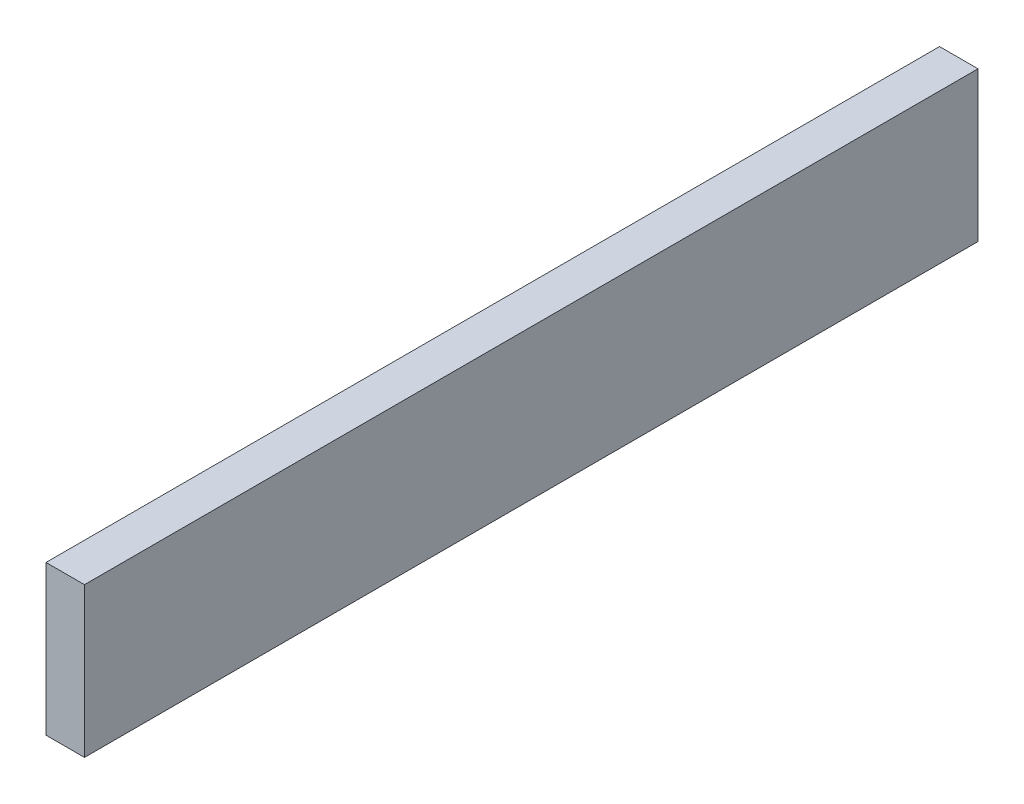
SolidWorks part; units mm, degrees
ref_plane "Front Plane" through (0, 0, 0) normal (0, 0, 1) x (1, 0, 0)
ref_plane "Top Plane" through (0, 0, 0) normal (0, 1, 0) x (1, 0, 0)
ref_plane "Right Plane" through (0, 0, 0) normal (1, 0, 0) x (0, 0, -1)
sketch "Sketch1" plane through (0, 0, 0) normal (1, 0, 0) x (0, 0, -1)
  line L1 (0, 0) -> (418, 0)
  line L2 (0, 0) -> (0, 70)
  line L3 (0, 70) -> (418, 70)
  line L4 (418, 0) -> (418, 70)
  dimension "D1" = 418
  dimension "D2" = 70
extrude "Boss-Extrude1" add sketch "Sketch1" along normal blind 18
